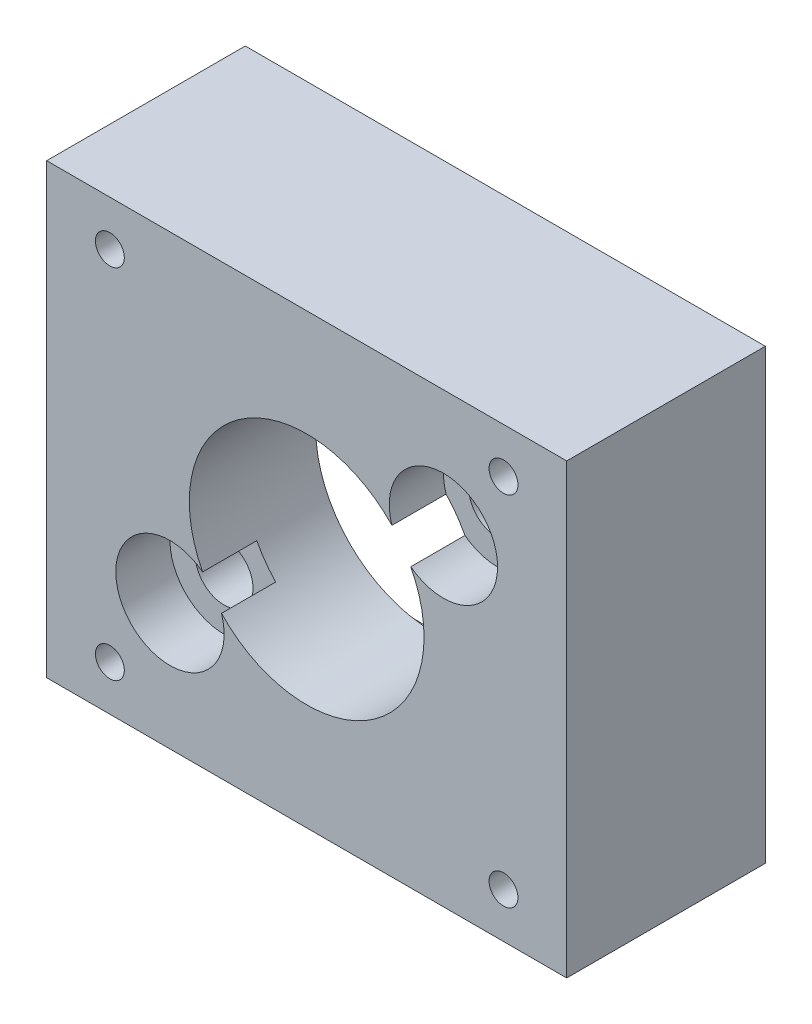
SolidWorks part; units mm, degrees
ref_plane "前视基准面" through (0, 0, 0) normal (0, 0, 1) x (1, 0, 0)
ref_plane "上视基准面" through (0, 0, 0) normal (0, 1, 0) x (1, 0, 0)
ref_plane "右视基准面" through (0, 0, 0) normal (1, 0, 0) x (0, 0, -1)
other "Configuration Table"
sketch "草图1" plane through (0, 0, 0) normal (0, 0, 1) x (1, 0, 0)
  line L5 (-7.2, 6.2) -> (7.2, 6.2)
  line L6 (-7.2, 6.2) -> (-7.2, -6.2)
  line L7 (-7.2, -6.2) -> (7.2, -6.2)
  line L8 (7.2, 6.2) -> (7.2, -6.2)
  line L9 (-7.2, 6.2) -> (7.2, -6.2) construction
  line L10 (-7.2, -6.2) -> (7.2, 6.2) construction
  point P0 (0, 0)
  dimension "D1" = 14.4
  dimension "D2" = 12.4
extrude "凸台-拉伸1" add sketch "草图1" along normal blind 3.5
sketch "草图3" plane through (0, 0, 3.5) normal (0, 0, 1) x (1, 0, 0)
  line L0 (-3.7858, -2.7) -> (3.7858, 2.7) construction
  circle A0 centre (3.7858, 2.7) radius 0.8
  circle A1 centre (-3.7858, -2.7) radius 0.8
  circle A2 centre (3.7858, 2.7) radius 1.5
  circle A3 centre (-3.7858, -2.7) radius 1.5
  circle A4 centre (0, 0) radius 3.25
  dimension "D3" = 3
  dimension "D4" = 1.6
  dimension "D5" = 6.5
  dimension "D1" = 5.4
  dimension "D2" = 9.3
extrude "切除-拉伸1" cut sketch "草图3" against normal through all contours A0 | A4 | A1
extrude "切除-拉伸2" cut sketch "草图3<3>" against normal offset from surface (1.5 mm away) 2 contours A3 | A2 up to face at (3.25, 0, 0)
sketch "草图3<3>" plane through (0, 0, 3.5) normal (0, 0, 1) x (1, 0, 0) same geometry as "草图3"
sketch "草图4" plane through (0, 0, 0) normal (0, 0, -1) x (-1, 0, 0)
  line L1 (-6.2, 5.2) -> (6.2, 5.2)
  line L2 (-6.2, 5.2) -> (-6.2, -5.2)
  line L3 (-6.2, -5.2) -> (6.2, -5.2)
  line L4 (6.2, 5.2) -> (6.2, -5.2)
  line L5 (-6.2, 5.2) -> (6.2, -5.2) construction
  line L6 (-6.2, -5.2) -> (6.2, 5.2) construction
  circle A0 centre (0, 0) radius 6.2
  point P0 (0, 0)
  point P5 (0, 0)
  line M9 (-7.2, 6.2) -> (-7.2, -6.2)
  line M10 (-7.2, -6.2) -> (7.2, -6.2)
  line M11 (7.2, -6.2) -> (7.2, 6.2)
  line M12 (7.2, 6.2) -> (-7.2, 6.2)
  dimension "D1" = 12.4
  dimension "D2" = 10.4
extrude "凸台-拉伸2" add sketch "草图4" along normal blind 2 contours A0 L3 L2 L1 M12 M9 M10 | A0 L1 L4 L3 M10 M11 M12 | L3 A0 | A0 L2 L3 | A0 L1 L2 | L1 A0 | A0 L4 L1 | A0 L3 L4 region at (6.3434, 2.6, 0) region at (5.4007, 3.9665, 0) region at (0, 5.6029, 0) region at (5.4007, -3.9665, 0) region at (-1.8014, 6.0822, 0) region at (-5.4007, 3.9665, 0) region at (0, -5.6029, 0) region at (-5.4007, -3.9665, 0)
sketch "草图5" plane through (0, 0, 3.5) normal (0, 0, 1) x (1, 0, 0)
  line L0 (7.2, 6.2) -> (-7.2, 6.2) construction
  line L1 (-7.2, 6.2) -> (-7.2, -6.2) construction
  line L2 (-7.2, -6.2) -> (7.2, -6.2) construction
  line L3 (7.2, -6.2) -> (7.2, 6.2) construction
  circle A0 centre (-5.45, 4.95) radius 0.4
  circle A1 centre (5.45, 4.95) radius 0.4
  circle A2 centre (5.45, -4.95) radius 0.4
  circle A3 centre (-5.45, -4.95) radius 0.4
  point P8 (0, 0)
  point P9 (0, 0)
  point P10 (0, 0)
  point P11 (0, 0)
  point P12 (0, 0)
  point P13 (-4.2837, 2.374)
  point P18 (5.3976, -5.3198)
  point P19 (4.0813, -5.2638)
  dimension "D3" = 0.8
  dimension "D1" = 1.25
  dimension "D2" = 1.75
  dimension "D4" = 1.25
  dimension "D5" = 1.75
extrude "切除-拉伸3" cut sketch "草图5" against normal through all
